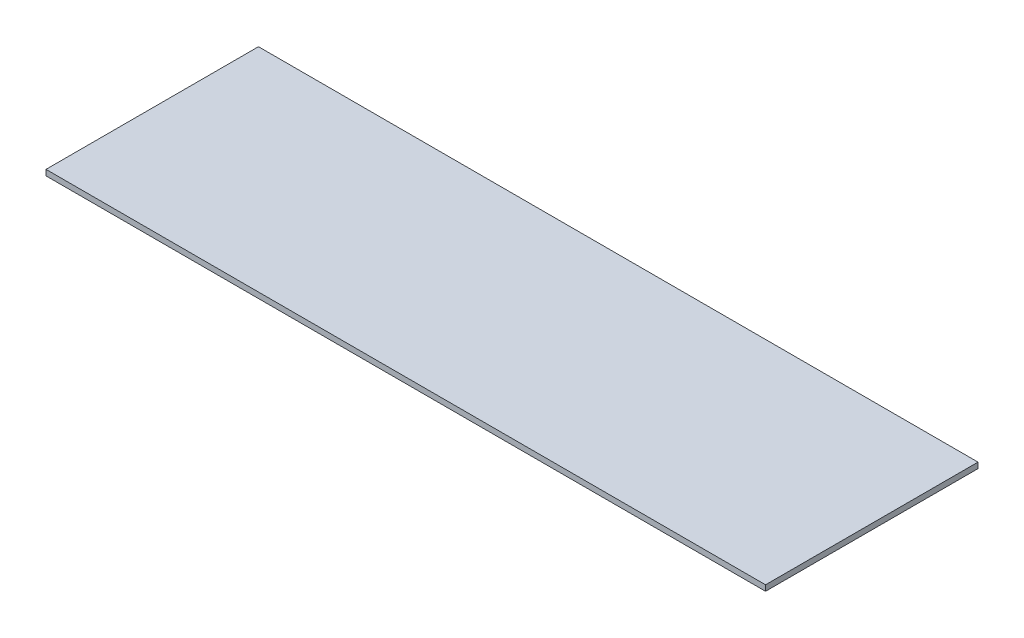
SolidWorks part; units mm, degrees
ref_plane "Front Plane" through (0, 0, 0) normal (0, 0, 1) x (1, 0, 0)
ref_plane "Top Plane" through (0, 0, 0) normal (0, 1, 0) x (1, 0, 0)
ref_plane "Right Plane" through (0, 0, 0) normal (1, 0, 0) x (0, 0, -1)
sketch "Sketch1" plane through (0, 0, 0) normal (0, 1, 0) x (1, 0, 0)
  line L1 (0, 0) -> (508, 0)
  line L2 (0, 0) -> (0, 150)
  line L3 (0, 150) -> (508, 150)
  line L4 (508, 0) -> (508, 150)
  dimension "D1" = 150
  dimension "D2" = 508
extrude "Boss-Extrude1" add sketch "Sketch1" along normal blind 4
equation "\"cf_tube_outer_diameter\" = 25mm"
equation "\"cf_tube_inner_diameter\" = 21mm"
equation "\"mid_plate_mid_to_top\" = 100mm"
equation "\"mid_plate_mid_to_bottom\" = 100mm"
equation "\"mid_plate_horizontal_spacing\" = 250mm"
equation "\"cf_plate_thickness\" = 4mm"
equation "\"mid_tube_length\" = 500mm"
equation "\"mid_plate_bottom_width\"= 150mm"
equation "\"D1@Sketch1\"=\"mid_plate_bottom_width\""
equation "\"D2@Sketch1\"=\"mid_tube_length\"+\"cf_plate_thickness\"*2"
equation "\"D1@Boss-Extrude1\"=\"cf_plate_thickness\""
